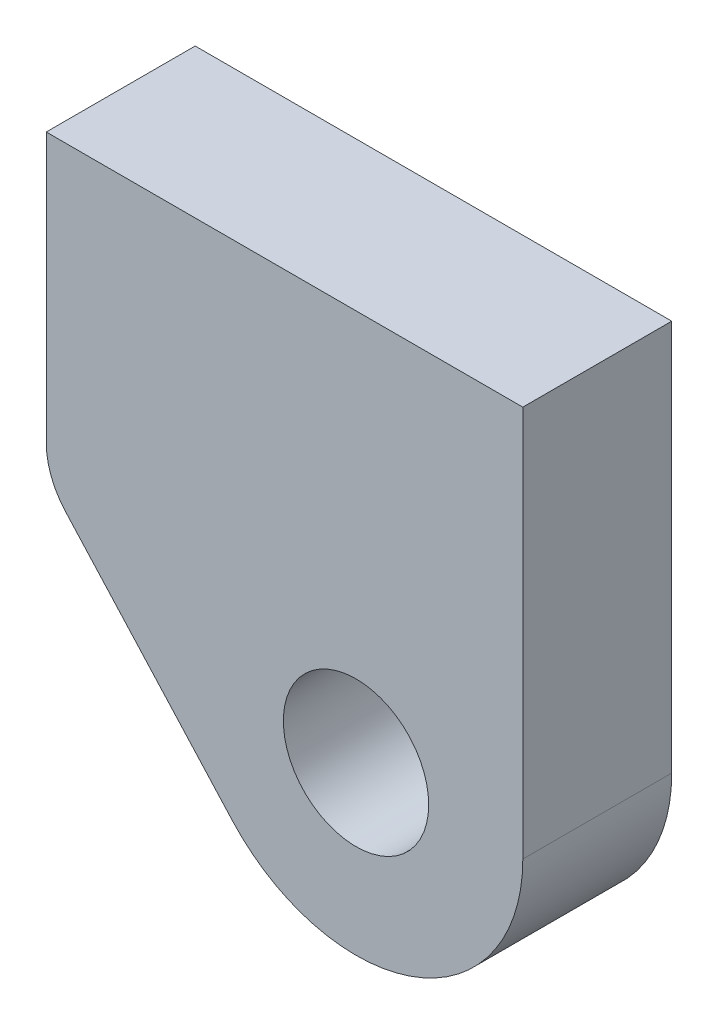
SolidWorks part; units mm, degrees
ref_plane "Front Plane" through (0, 0, 0) normal (0, 0, 1) x (1, 0, 0)
ref_plane "Top Plane" through (0, 0, 0) normal (0, 1, 0) x (1, 0, 0)
ref_plane "Right Plane" through (0, 0, 0) normal (1, 0, 0) x (0, 0, -1)
sketch "Sketch1" plane through (0, 0, 0) normal (0, 0, 1) x (1, 0, 0)
  line L0 (-5.08, 0) -> (5.08, 0)
  line L1 (-5.08, 0) -> (-5.08, -5.7379)
  line L2 (5.08, 0) -> (5.08, -8.3439)
  line L3 (-4.6691, -6.8037) -> (-1.1115, -10.7312)
  arc A0 (5.08, -8.3439) -> (-1.1115, -10.7312) centre (1.524, -8.3439) cw
  circle A1 centre (1.524, -8.3439) radius 1.5494
  arc A2 (-4.6691, -6.8037) -> (-5.08, -5.7379) centre (-3.4925, -5.7379) cw
  point P4 (0, 0)
  point P12 (-5.08, -6.35)
  dimension "D4" = 3.556
  dimension "D5" = 3.0988
  dimension "D6" = 1.5875
  dimension "D1" = 10.16
  dimension "D2" = 6.35
  dimension "D3" = 8.3439
extrude "Boss-Extrude1" add sketch "Sketch1" along normal mid plane 3.175 contours A0 L2 L0 L1 L3 A1 region at (0.2551, -5.0038, 0)
